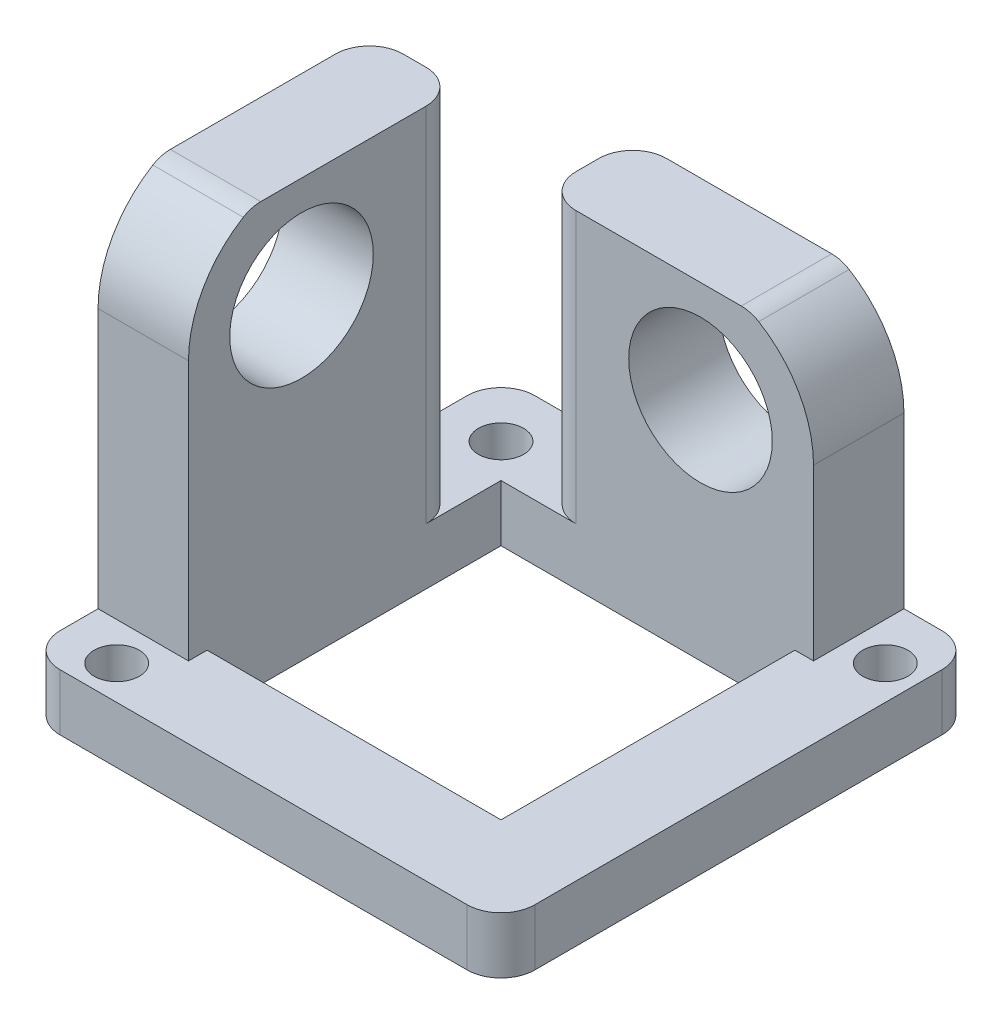
SolidWorks part; units mm, degrees
ref_plane "前视基准面" through (0, 0, 0) normal (0, 0, 1) x (1, 0, 0)
ref_plane "上视基准面" through (0, 0, 0) normal (0, 1, 0) x (1, 0, 0)
ref_plane "右视基准面" through (0, 0, 0) normal (1, 0, 0) x (0, 0, -1)
sketch "草图1" plane through (0, 0, 0) normal (0, 1, 0) x (1, 0, 0)
  line L0 (39, 0) -> (39, 37) construction
  line L1 (3, 0) -> (39, 0)
  line L2 (0, 3) -> (0, 39)
  line L3 (3, 42) -> (39, 42)
  line L4 (42, 3) -> (42, 39)
  line L9 (42, 37) -> (5, 37) construction
  line L10 (5, 37) -> (39, 37) construction
  line L11 (5, 37) -> (5, 3) construction
  line L13 (8, 34) -> (34, 34)
  line L14 (8, 34) -> (8, 8)
  line L15 (8, 8) -> (34, 8)
  line L16 (34, 34) -> (34, 8)
  arc A0 (3, 42) -> (0, 39) centre (3, 39) ccw
  arc A1 (3, 0) -> (0, 3) centre (3, 3) cw
  arc A2 (42, 3) -> (39, 0) centre (39, 3) cw
  arc A3 (42, 39) -> (39, 42) centre (39, 39) ccw
  circle A4 centre (5, 37) radius 2
  circle A5 centre (39, 37) radius 2
  circle A6 centre (5, 3) radius 2
  point P9 (0, 0)
  dimension "D1" = 3
  dimension "D2" = 3
  dimension "D5" = 8
  dimension "D3" = 37
  dimension "D4" = 37
  dimension "D6" = 8
  dimension "D7" = 8
  dimension "D8" = 8
extrude "凸台-拉伸1" add sketch "草图1" along normal blind 5
sketch "草图2" plane through (0, 5, 0) normal (0, 1, 0) x (1, 0, 0)
  line L0 (5, 37) -> (25.65, 37) construction
  line L1 (35.65, 42) -> (35.65, 34)
  line L2 (39, 42) -> (3, 42) construction
  line L3 (34, 34) -> (8, 34) construction
  line L4 (35.65, 34) -> (11.65, 34)
  line L5 (11.65, 34) -> (11.65, 42)
  line L6 (11.65, 42) -> (35.65, 42)
  line L7 (5, 37) -> (5, 16.35) construction
  line L8 (0, 30.35) -> (8, 30.35)
  line L9 (0, 39) -> (0, 3) construction
  line L10 (8, 34) -> (8, 8) construction
  line L11 (8, 30.35) -> (8, 6.35)
  line L12 (8, 6.35) -> (0, 6.35)
  line L13 (0, 6.35) -> (0, 30.35)
  line M4 (0, 39) -> (0, 3)
  line M10 (39, 42) -> (3, 42)
  line M14 (8, 8) -> (8, 34)
  line M15 (8, 34) -> (34, 34)
  dimension "D1" = 24
  dimension "D2" = 10
  dimension "D3" = 20.65
  dimension "D4" = 20.65
  dimension "D5" = 24
  dimension "D6" = 10
extrude "凸台-拉伸2" add sketch "草图2" along normal blind 24 contours L5 L4 L1 M15 M10 region at (23.65, 5, -38)
extrude "凸台-拉伸3" add sketch "草图2<3>" along normal blind 32 contours L12 L11 L8 M14 M4 region at (4, 5, -18.35)
sketch "草图2<3>" plane through (0, 5, 0) normal (0, 1, 0) x (1, 0, 0) same geometry as "草图2"
sketch "草图3" plane through (0, 0, -42) normal (0, 0, -1) x (-1, 0, 0)
  line L0 (-35.65, 29) -> (-35.65, 5) construction
  line L1 (-39, 0) -> (-3, 0) construction
  line L2 (-35.65, 29) -> (-11.65, 29) construction
  line L3 (-35.65, 29) -> (-11.65, 29)
  line L4 (-35.65, 29) -> (-35.65, 5)
  circle A0 centre (-25.65, 20) radius 6.35
  arc A2 (-30.0089, 29) -> (-35.65, 20) centre (-25.65, 20) ccw
  line M9 (-35.65, 29) -> (-35.65, 5)
  dimension "D3" = 12.7
  dimension "D1" = 10
  dimension "D2" = 20
extrude "切除-拉伸1" cut sketch "草图3" against normal up to next contours A0 | A2 L3 M9 region at (34.0896, 26.8956, -42) region at (25.65, 20, -42)
sketch "草图4" plane through (8, 0, 0) normal (1, 0, 0) x (0, 0, -1)
  line L0 (6.35, 37) -> (6.35, 5) construction
  line L2 (3, 0) -> (39, 0) construction
  line L3 (30.35, 37) -> (6.35, 37) construction
  line L4 (6.35, 37) -> (6.35, 5)
  line L5 (30.35, 37) -> (6.35, 37)
  circle A0 centre (16.35, 28) radius 6.35
  arc A1 (11.9911, 37) -> (6.35, 28) centre (16.35, 28) ccw
  line M6 (6.35, 37) -> (6.35, 5)
  dimension "D3" = 12.7
  dimension "D1" = 10
  dimension "D2" = 28
extrude "切除-拉伸2" cut sketch "草图4" against normal up to next contours A0 | A1 L5 M6 region at (8, 34.8956, -7.9104) region at (8, 28, -16.35)
fillet "圆角2" radius 3 6 edges at (30.0089, 29, -38) (11.65, 17, -42) (11.65, 17, -34) (4, 37, -11.9911) (0, 21, -30.35) (8, 21, -30.35)
